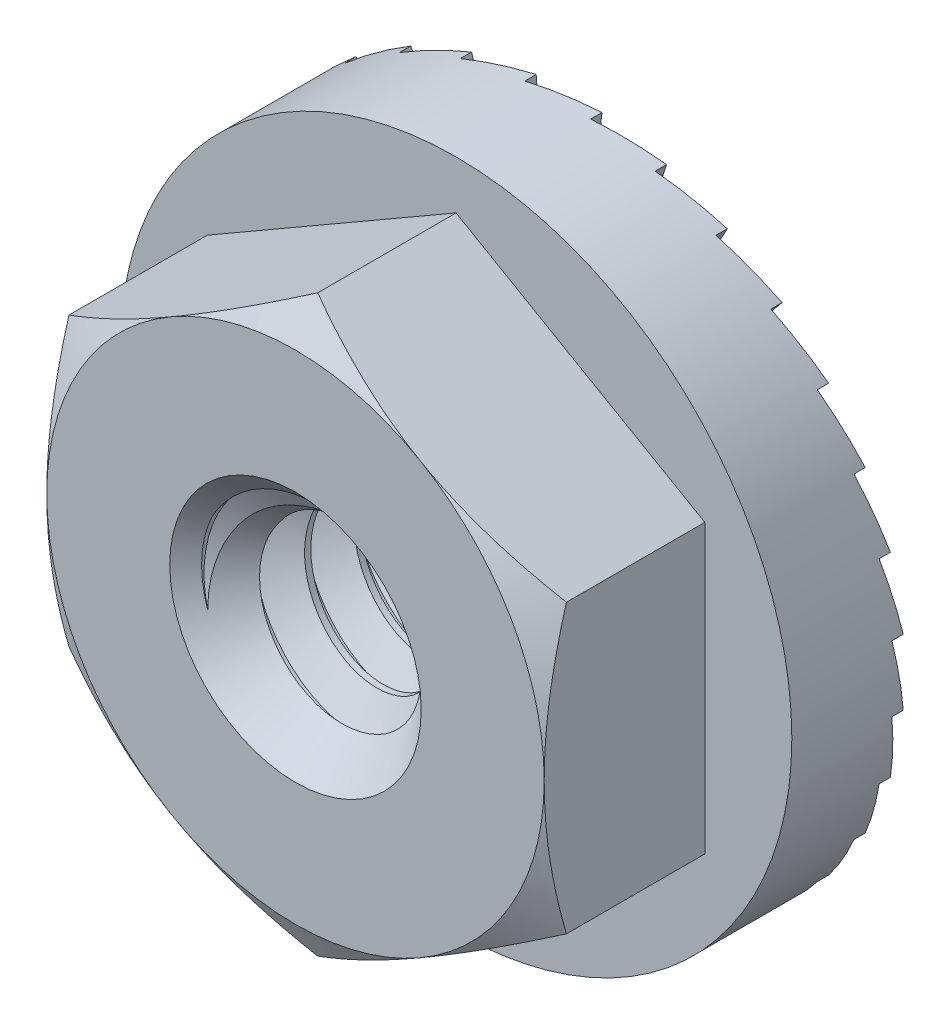
SolidWorks part; units mm, degrees
ref_plane "Front Plane" through (0, 0, 0) normal (0, 0, 1) x (1, 0, 0)
ref_plane "Top Plane" through (0, 0, 0) normal (0, 1, 0) x (1, 0, 0)
ref_plane "Right Plane" through (0, 0, 0) normal (1, 0, 0) x (0, 0, -1)
sketch "Sketch1" plane through (0, 0, 0) normal (0, 0, 1) x (1, 0, 0)
  line L1 (0, 4.5827) -> (-3.9688, 2.2914)
  line L2 (-3.9688, 2.2914) -> (-3.9688, -2.2914)
  line L3 (-3.9688, -2.2914) -> (0, -4.5827)
  line L4 (0, -4.5827) -> (3.9687, -2.2914)
  line L5 (3.9687, -2.2914) -> (3.9687, 2.2914)
  line L6 (3.9687, 2.2914) -> (0, 4.5827)
  circle A0 centre (0, 0) radius 3.9688 construction
  dimension "Hex" = 7.9375
extrude "Extrude1" add sketch "Sketch1" against normal blind 4.3656
sketch "Sketch13" plane through (0, 0, -4.3656) normal (0, 0, -1) x (-1, 0, 0)
  circle A0 centre (0, 0) radius 5.3578
  dimension "Flange od" = 10.7156
extrude "Extrude3" add sketch "Sketch13" against normal blind 1.8034
sketch "Sketch2" plane through (0, 0, 0) normal (0, 0, 1) x (1, 0, 0)
  circle A0 centre (0, 0) radius 3.9688 construction
  circle A1 centre (0, 0) radius 3.9688
extrude "Cut-Extrude1" cut sketch "Sketch2" against normal through all draft 60 flip side to cut
sketch "Sketch4" plane through (0, 0, 0) normal (0, 0, 1) x (1, 0, 0)
  circle A0 centre (0, 0) radius 1.7526
  dimension "Thread Dia" = 3.5052
extrude "Cut-Extrude3" cut sketch "Sketch4" against normal through all
sketch "Sketch7" plane through (0, 0, 0) normal (0, 0, 1) x (1, 0, 0)
  circle A4 centre (0, 0) radius 2.0066
  circle A5 centre (0, 0) radius 2.0066
  dimension "D1" = 0.254
sketch "Sketch8" plane through (0, 0, -4.3656) normal (0, 0, -1) x (-1, 0, 0)
  circle A1 centre (0, 0) radius 2.0066
  circle A2 centre (0, 0) radius 2.0066 construction
sketch "Sketch5" plane through (0, 0, 0) normal (0, 0, 1) x (1, 0, 0)
  circle A0 centre (0, 0) radius 1.7526 construction
  circle A1 centre (0, 0) radius 1.7526
curve "Helix/Spiral1" pitch 0.7937 height 5.1594 turns 6.5 parameters "pitch"=0.7937
sketch "Sketch9" plane through (0, 0, 0) normal (1, 0, 0) x (0, 0, -1)
  line L0 (-0.3969, 1.7526) -> (-0.2977, 1.7526)
  line L1 (-0.2977, 1.7526) -> (0, 1.237)
  line L2 (-0.3969, 1.7526) -> (-0.6945, 1.237)
  line L3 (-0.6945, 1.237) -> (0, 1.237)
  line L4 (-0.3473, 1.7526) -> (-0.3473, 1.237) construction
  line L5 (-0.5457, 1.4948) -> (-0.1488, 1.4948) construction
  line L7 (0, 1.237) -> (0, 1.7526) construction
  line L8 (0, 1.7526) -> (0, -1.7526) construction
  dimension "D1" = 0.0992
  dimension "D2" = 0.3969
  dimension "D3" = 60
sketch "Sketch12" plane through (0, 0, 0) normal (0, 0, 1) x (1, 0, 0)
  circle A0 centre (0, 0) radius 1.237
  circle A1 centre (0, 0) radius 1.7526 construction
  circle A2 centre (0, 0) radius 1.7526
extrude "Extrude2" add sketch "Sketch12" against normal up to surface (4.3656 mm away)
sweep "Cut-Sweep1" cut profiles "Sketch9" path "Helix/Spiral1"
extrude "Cut-Extrude6" cut sketch "Sketch7" against normal through all draft 45
extrude "Cut-Extrude7" cut sketch "Sketch8" against normal through all draft 45
sketch "Sketch14" plane through (0, 0, -4.3656) normal (0, 0, -1) x (-1, 0, 0)
  circle A4 centre (0, 0) radius 4.0386
  circle A5 centre (0, 0) radius 4.0386
  dimension "D1" = 2.032
extrude "Cut-Extrude8" cut sketch "Sketch14" against normal blind 0.1803 flip side to cut
sketch "Sketch15" plane through (0, 0, -4.1853) normal (0, 0, -1) x (-1, 0, 0)
  line L0 (-0.3959, 4.0192) -> (-0.5252, 5.332)
  line L1 (0.3959, 4.0192) -> (0.5252, 5.332)
  line L2 (0, 0) -> (0.3959, 4.0192) construction
  line L3 (0, 0) -> (-0.3959, 4.0192) construction
  circle A0 centre (0, 0) radius 5.3578 construction
  circle A1 centre (0, 0) radius 4.0386 construction
  arc A2 (0.5252, 5.332) -> (-0.5252, 5.332) centre (0, 0) ccw
  arc A3 (0.3959, 4.0192) -> (-0.3959, 4.0192) centre (0, 0) ccw
  dimension "D1" = 11.25
extrude "Extrude4" add sketch "Sketch15" along normal up to surface (0.1803 mm away) separate body up to face at (-2.0066, 0, -4.3656)
sketch "Sketch16" plane through (0, 0, 0) normal (0, 1, 0) x (1, 0, 0)
  line L0 (-0.5252, 4.1853) -> (0.5252, 4.3656)
  line L4 (-0.5252, 4.1853) -> (0.5252, 4.1853)
  line L5 (0.5252, 4.1853) -> (0.5252, 4.3656)
  line L6 (0.5252, 4.3656) -> (-0.5252, 4.3656)
  line L7 (-0.5252, 4.3656) -> (-0.5252, 4.1853)
  line L8 (-0.5252, 4.1853) -> (0.5252, 4.1853) construction
  line L9 (0.5252, 4.1853) -> (0.5252, 4.3656) construction
  line L10 (0.5252, 4.3656) -> (-0.5252, 4.3656)
  line L11 (-0.5252, 4.3656) -> (-0.5252, 4.1853)
  dimension "D1" = 0
extrude "Cut-Extrude9" cut sketch "Sketch16" along normal through all
pattern_circular "CirPattern1" count 32 over 360 about axis through (0, 0, 0) along (0, 0, 1) of bodies 119
combine bodies "Combine1" operation type add bodies to combine 117 119 120 121 122 123 124 125 126 127 128 129 130 131 132 133 134 135 136 137 139 140 141 142 143 144 145 146 147 148 149 150 151
sketch "Sketch17" plane through (0, 0, 0) normal (1, 0, 0) x (0, 0, -1)
  line L0 (4.3656, 5.3578) -> (4.3656, -5.3578) construction
  line L1 (2.5622, 5.3578) -> (2.5622, -5.3578) construction
  dimension "D1" = 1.8034
sketch "Sketch18" plane through (0, 0, -2.5622) normal (0, 0, 1) x (1, 0, 0)
  circle A0 centre (0, 0) radius 5.3578
  circle A1 centre (0, 0) radius 5.3578 construction
equation "\"D2@Sketch9\" = \"pitch@Helix/Spiral1\"*.5"
equation "\"D3@Helix/Spiral1\" = \"pitch@Helix/Spiral1\"+\"Height@Extrude1\""
equation "\"D1@Sketch9\" = \"pitch@Helix/Spiral1\"*.125"
equation "\"D1@Cut-Extrude8\" = \"flange thickness@Extrude3\"*.1"
equation "\"D1@Sketch17\" = \"flange thickness@Extrude3\""
